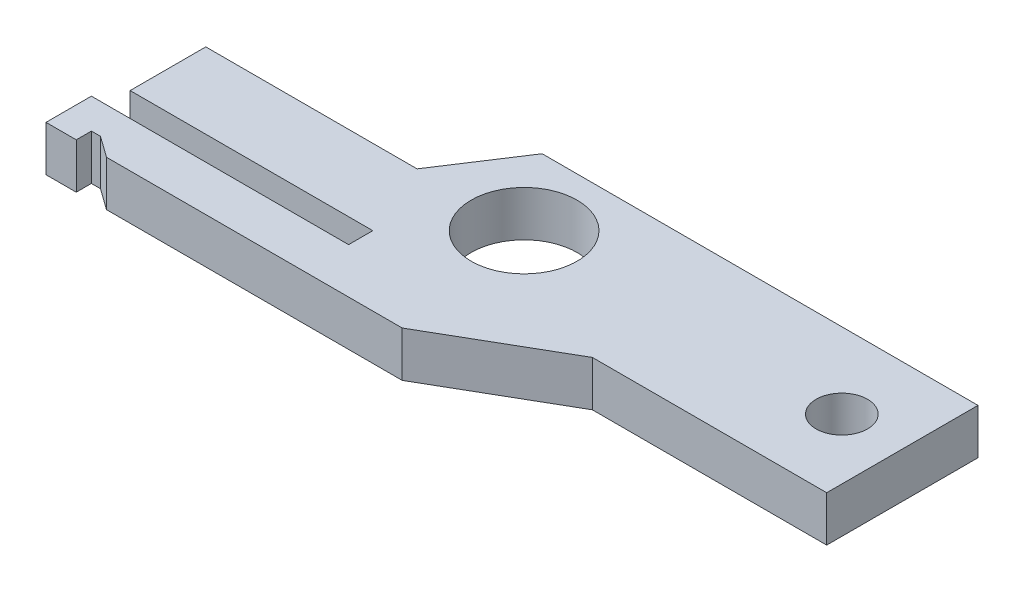
SolidWorks part; units mm, degrees
ref_plane "前视基准面" through (0, 0, 0) normal (0, 0, 1) x (1, 0, 0)
ref_plane "上视基准面" through (0, 0, 0) normal (0, 1, 0) x (1, 0, 0)
ref_plane "右视基准面" through (0, 0, 0) normal (1, 0, 0) x (0, 0, -1)
sketch "草图2" plane through (0, 7.0968, 0) normal (0, 1, 0) x (1, 0, 0)
  line L0 (-1.9, 0) -> (-10.4, 0)
  line L1 (-6.9, 0.7) -> (-6.9, 0) construction
  line L2 (-1.9, 0) -> (-1.9, 0.8)
  line L3 (-1.9, 0.8) -> (-9.9195, 0.8)
  line L4 (-6.9, 0.7) -> (-1.9, 0.7) construction
  line L5 (-10.4, 0) -> (-10.4, -1.5)
  line L6 (-10.4, -1.5) -> (-9.4, -1.5)
  line L7 (13.1, 0.8) -> (13.1, 5.8)
  line L8 (-9.4, -1) -> (-9.1, -1)
  line L9 (-9.1, -1) -> (-8.4, -1.5)
  line L10 (-1.3034, 5.8) -> (-2.9368, 3.3)
  line L11 (13.1, 5.8) -> (-1.3034, 5.8)
  line L12 (-9.9195, 3.3) -> (-9.9195, 0.8)
  line L13 (-9.4, -1.5) -> (-9.4, -1)
  line L15 (1.3718, -1.5) -> (5.3555, 0.8)
  line L16 (5.3555, 0.8) -> (13.1, 0.8)
  line L17 (-8.4, -1.5) -> (1.3718, -1.5)
  line L18 (-2.9368, 3.3) -> (-9.9195, 3.3)
  circle A0 centre (11.1, 3.3) radius 0.85
  circle A1 centre (0.6, 3.3) radius 1.75
  point P12 (-8.4, 0.8)
  dimension "D4" = 1.7
  dimension "D5" = 3.5
  dimension "D1" = 0.1
  dimension "D2" = 1.5
  dimension "D6" = 10.5
  dimension "D7" = 1
  dimension "D8" = 2.5
  dimension "D9" = 0.5
  dimension "D10" = 10
  dimension "D12" = 1
  dimension "D13" = 2
  dimension "D14" = 30
  dimension "D15" = 2.5
  dimension "D3" = 5
  dimension "D16" = 0.3
extrude "凸台-拉伸1" add sketch "草图2" against normal blind 1.5
equation "\"D8@草图2\"=\"D3@草图2\"/2"
